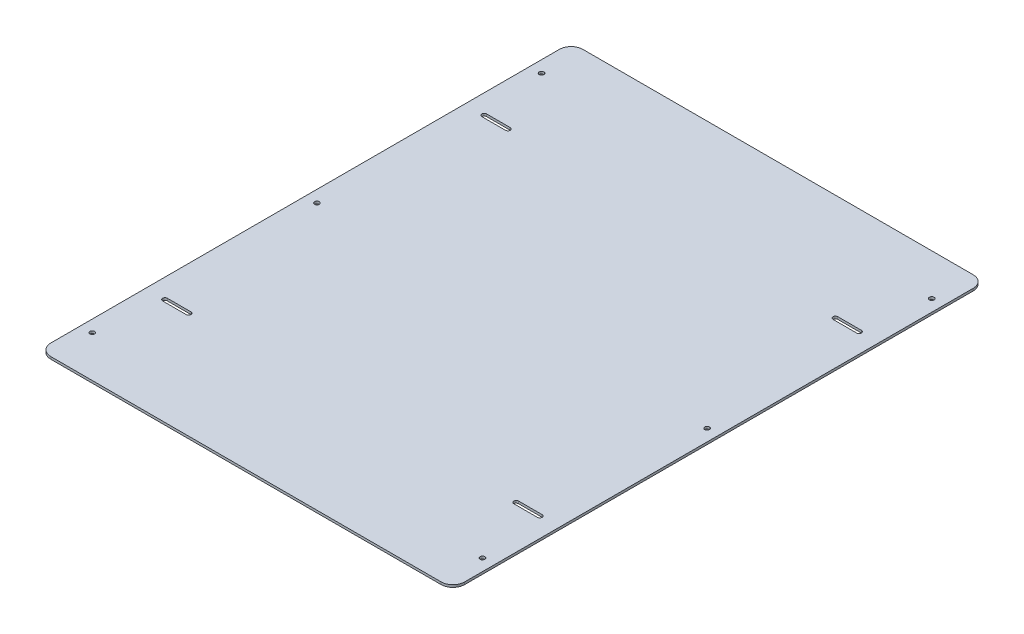
SolidWorks part; units mm, degrees
material "1060 合金"
ref_plane "前视基准面" through (0, 0, 0) normal (0, 0, 1) x (1, 0, 0)
ref_plane "上视基准面" through (0, 0, 0) normal (0, 1, 0) x (1, 0, 0)
ref_plane "右视基准面" through (0, 0, 0) normal (1, 0, 0) x (0, 0, -1)
sketch "草图1" plane through (0, 0, 0) normal (0, 1, 0) x (1, 0, 0)
  line L0 (-158.5, 135) -> (-138.5, 135) construction
  line L1 (-165, 225) -> (165, 225)
  line L2 (-175, 215) -> (-175, -215)
  line L3 (-165, -225) -> (165, -225)
  line L4 (175, 215) -> (175, -215)
  line L5 (-175, 225) -> (175, -225) construction
  line L6 (-175, -225) -> (175, 225) construction
  line L9 (-158.5, 137) -> (-138.5, 137)
  line L12 (-158.5, 133) -> (-138.5, 133)
  line L15 (138.5, 135) -> (158.5, 135) construction
  line L18 (138.5, 137) -> (158.5, 137)
  line L19 (138.5, 133) -> (158.5, 133)
  line L20 (0, 0) -> (-50000, 0) construction
  line L21 (-158.5, -135) -> (-138.5, -135) construction
  line L22 (-158.5, -137) -> (-138.5, -137)
  line L23 (-158.5, -133) -> (-138.5, -133)
  line L24 (138.5, -135) -> (158.5, -135) construction
  line L25 (138.5, -137) -> (158.5, -137)
  line L26 (138.5, -133) -> (158.5, -133)
  arc A0 (-175, -215) -> (-165, -225) centre (-165, -215) ccw
  arc A1 (165, -225) -> (175, -215) centre (165, -215) ccw
  arc A2 (165, 225) -> (175, 215) centre (165, 215) cw
  arc A3 (-165, 225) -> (-175, 215) centre (-165, 215) ccw
  circle A19 centre (-165, 190) radius 2
  circle A20 centre (165, 190) radius 2
  circle A21 centre (165, 0) radius 2
  circle A22 centre (165, -190) radius 2
  circle A23 centre (-165, -190) radius 2
  circle A24 centre (-165, 0) radius 2
  arc A25 (-158.5, 137) -> (-158.5, 133) centre (-158.5, 135) ccw
  arc A26 (-138.5, 133) -> (-138.5, 137) centre (-138.5, 135) ccw
  arc A27 (138.5, 137) -> (138.5, 133) centre (138.5, 135) ccw
  arc A28 (158.5, 133) -> (158.5, 137) centre (158.5, 135) ccw
  arc A29 (-158.5, -137) -> (-158.5, -133) centre (-158.5, -135) cw
  arc A30 (-138.5, -133) -> (-138.5, -137) centre (-138.5, -135) cw
  arc A31 (138.5, -137) -> (138.5, -133) centre (138.5, -135) cw
  arc A32 (158.5, -133) -> (158.5, -137) centre (158.5, -135) cw
  point P0 (0, 0)
  point P32 (-148.5, 135)
  point P38 (148.5, 135)
  point P47 (0, 0)
  point P49 (-148.5, -135)
  point P56 (148.5, -135)
  dimension "D3" = 10
  dimension "D4" = 4
  dimension "D5" = 4
  dimension "D6" = 4
  dimension "D7" = 4
  dimension "D11" = 10
  dimension "D12" = 10
  dimension "D15" = 415
  dimension "D17" = 10
  dimension "D18" = 10
  dimension "D19" = 35
  dimension "D20" = 225
  dimension "D24" = 2
  dimension "D27" = 2
  dimension "D8" = 4
  dimension "D9" = 4
  dimension "D10" = 10
  dimension "D13" = 35
  dimension "D16" = 10
  dimension "D21" = 415
  dimension "D1" = 350
  dimension "D2" = 450
  dimension "D14" = 225
  dimension "D22" = 26.5
  dimension "D23" = 20
  dimension "D25" = 26.5
  dimension "D26" = 20
  dimension "D28" = 90
base flange "基体-法兰1" sketch "草图1" thickness 2 reverse thickness direction no parameters "D1"=0.7366
sketch "折弯-线1" [suppressed] plane through (0, 0, 0) normal (0, 1, 0) x (1, 0, 0)
sketch "边界框1" [suppressed] plane through (0, 0, 0) normal (0, 1, 0) x (1, 0, 0)
sheet metal parameters "钣金12" thickness 2 parameters "D1"=0.7366
flat pattern "平板型式12" [suppressed]
sketch "折弯-线2" plane through (0, 0, 0) normal (0, 1, 0) x (1, 0, 0)
sketch3d "边界框2" [suppressed]
  line L0 (-10, -10, 0) -> (290, -10, 0) construction
  line L1 (-10, 190, 0) -> (290, 190, 0) construction
  line L2 (-10, -10, 0) -> (-10, 190, 0) construction
  line L3 (290, -10, 0) -> (290, 190, 0) construction
